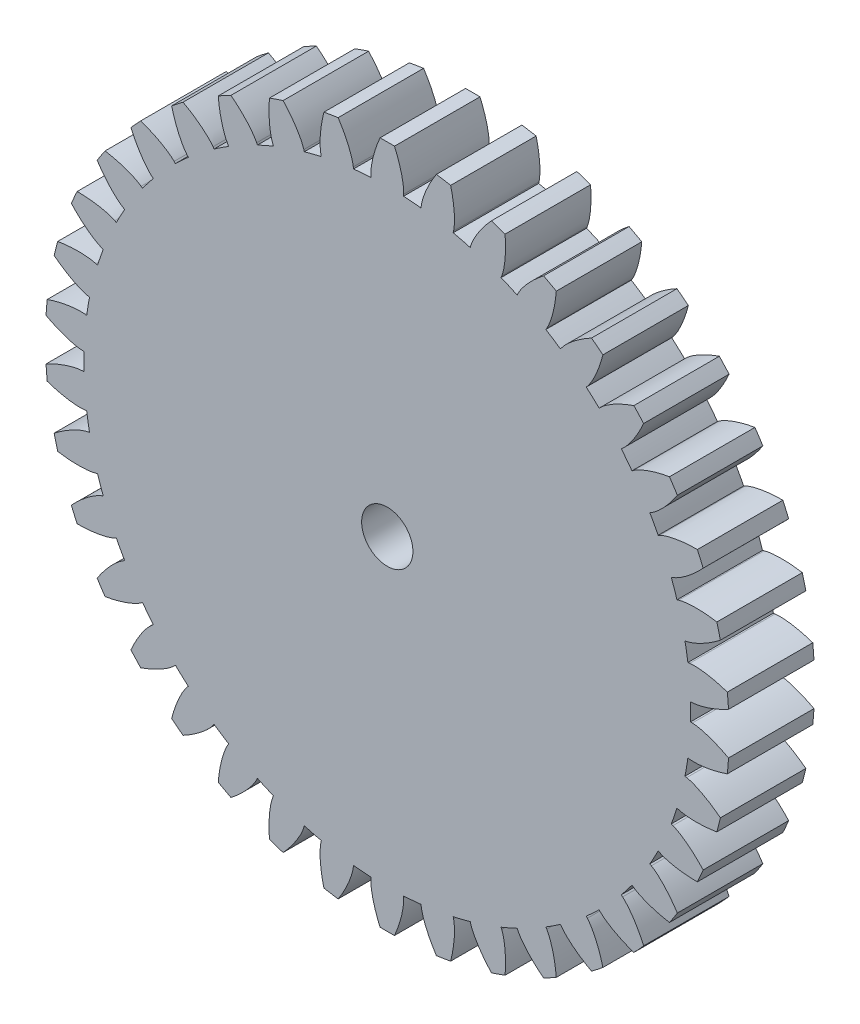
SolidWorks part; units mm, degrees
ref_plane "前视基准面" through (0, 0, 0) normal (0, 0, 1) x (1, 0, 0)
ref_plane "上视基准面" through (0, 0, 0) normal (0, 1, 0) x (1, 0, 0)
ref_plane "右视基准面" through (0, 0, 0) normal (1, 0, 0) x (0, 0, -1)
other "Configuration Table"
sketch "草图1" plane through (0, 0, 0) normal (0, 0, 1) x (1, 0, 0)
  line L0 (0, 0) -> (19, 0) construction
  line L1 (0, 0) -> (18.9838, 0.7852) construction
  line L2 (0, 0) -> (17.8467, 0.5157)
  line L3 (18.9838, 0.7852) -> (18.9838, -0.7852) construction
  line L4 (0, 0) -> (17.8467, -0.5157)
  circle A0 centre (0, 0) radius 20
  circle A1 centre (0, 0) radius 19 construction
  circle A2 centre (0, 0) radius 17.75
  circle A3 centre (0, 0) radius 17.8542 construction
  circle A4 centre (0, 0) radius 1.5
  spline S0 degree 4 poles (17.8467, 0.5157) (17.8807, 0.5167) (17.9484, 0.5207) (18.0833, 0.537) (18.3375, 0.584) (18.6733, 0.6727) (19.1324, 0.8321) (19.6729, 1.0705) (20.4872, 1.506) (21.549, 2.2345) (22.8952, 3.4297) (24.3758, 5.2063) (25.7051, 7.3713) (26.8016, 9.8792) (27.5793, 12.502) (28.0558, 15.1949) (28.2576, 18.0569) (28.1368, 21.6081) (27.4506, 25.7959) (25.9511, 30.4951) (23.4989, 35.3947) (20.7605, 39.3269) (18.0528, 42.4068) (15.5858, 44.7666) (13.4967, 46.526) (11.3039, 48.1534) (9.0163, 49.6461) (6.0541, 51.3408) (2.3486, 53.0976) (-2.1434, 54.7391) (-6.4614, 55.8085) (-9.8217, 56.3712) (-12.2052, 56.6454) (-13.5383, 56.7677) (-14.8361, 56.8491) (-15.854, 56.8967) (-16.9306, 56.9208) (-17.4967, 56.9272) (-18.1867, 56.9272) (-18.7351, 56.9214) (-19.419, 56.9074) (-20.2481, 56.8799) (-21.2082, 56.8323) (-22.3086, 56.7568) (-23.4047, 56.6603) (-24.5006, 56.543) (-25.3196, 56.4395) (-25.8654, 56.3637) (-26.1377, 56.3241) knots 0 0 0 0 0 0.001401 0.002802 0.005604 0.010661 0.015718 0.022839 0.02996 0.048734 0.068727 0.096889 0.125051 0.153212 0.181374 0.209535 0.237696 0.271429 0.327752 0.384075 0.440398 0.496721 0.524883 0.553044 0.581206 0.609367 0.637529 0.66569 0.722013 0.778336 0.834659 0.84874 0.86282 0.876901 0.890982 0.900036 0.909091 0.914773 0.920455 0.926136 0.931818 0.943182 0.954545 0.965909 0.977273 0.988636 1 1 1 1 1 construction
  spline S1 degree 4 poles (17.8467, 0.5157) (17.8807, 0.5167) (17.9484, 0.5207) (18.0833, 0.537) (18.3375, 0.584) (18.6733, 0.6727) (19.1324, 0.8321) (19.6729, 1.0705) (20.4872, 1.506) (21.549, 2.2345) (22.8952, 3.4297) (24.3758, 5.2063) (25.7051, 7.3713) (26.8016, 9.8792) (27.5793, 12.502) (28.0558, 15.1949) (28.2576, 18.0569) (28.1368, 21.6081) (27.4506, 25.7959) (25.9511, 30.4951) (23.4989, 35.3947) (20.7605, 39.3269) (18.0528, 42.4068) (15.5858, 44.7666) (13.4967, 46.526) (11.3039, 48.1534) (9.0163, 49.6461) (6.0541, 51.3408) (2.3486, 53.0976) (-2.1434, 54.7391) (-6.4614, 55.8085) (-9.8217, 56.3712) (-12.2052, 56.6454) (-13.5383, 56.7677) (-14.8361, 56.8491) (-15.854, 56.8967) (-16.7691, 56.9172) (-17.1568, 56.9229) (-17.3562, 56.9247) knots 0 0 0 0 0 0.001401 0.002802 0.005604 0.010661 0.015718 0.022839 0.02996 0.048734 0.068727 0.096889 0.125051 0.153212 0.181374 0.209535 0.237696 0.271429 0.327752 0.384075 0.440398 0.496721 0.524883 0.553044 0.581206 0.609367 0.637529 0.66569 0.722013 0.778336 0.834659 0.84874 0.86282 0.876901 0.890982 0.900036 0.909091 0.909091 0.909091 0.909091 0.909091
  spline S2 degree 4 poles (17.8467, -0.5157) (17.8807, -0.5167) (17.9484, -0.5207) (18.0833, -0.537) (18.3375, -0.584) (18.6733, -0.6727) (19.1324, -0.8321) (19.6729, -1.0705) (20.4872, -1.506) (21.549, -2.2345) (22.8952, -3.4297) (24.3758, -5.2063) (25.7051, -7.3713) (26.8016, -9.8792) (27.5793, -12.502) (28.0558, -15.1949) (28.2576, -18.0569) (28.1368, -21.6081) (27.4506, -25.7959) (25.9511, -30.4951) (23.4989, -35.3947) (20.7605, -39.3269) (18.0528, -42.4068) (15.5858, -44.7666) (13.4967, -46.526) (11.3039, -48.1534) (9.0163, -49.6461) (6.0541, -51.3408) (2.3486, -53.0976) (-2.1434, -54.7391) (-6.4614, -55.8085) (-9.8217, -56.3712) (-12.2052, -56.6454) (-13.5383, -56.7677) (-14.8361, -56.8491) (-15.854, -56.8967) (-16.9306, -56.9208) (-17.4967, -56.9272) (-18.1867, -56.9272) (-18.7351, -56.9214) (-19.419, -56.9074) (-20.2481, -56.8799) (-21.2082, -56.8323) (-22.3086, -56.7568) (-23.4047, -56.6603) (-24.5006, -56.543) (-25.3196, -56.4395) (-25.8654, -56.3637) (-26.1377, -56.3241) knots 0 0 0 0 0 0.001401 0.002802 0.005604 0.010661 0.015718 0.022839 0.02996 0.048734 0.068727 0.096889 0.125051 0.153212 0.181374 0.209535 0.237696 0.271429 0.327752 0.384075 0.440398 0.496721 0.524883 0.553044 0.581206 0.609367 0.637529 0.66569 0.722013 0.778336 0.834659 0.84874 0.86282 0.876901 0.890982 0.900036 0.909091 0.914773 0.920455 0.926136 0.931818 0.943182 0.954545 0.965909 0.977273 0.988636 1 1 1 1 1 construction
  spline S3 degree 4 poles (17.8467, -0.5157) (17.8807, -0.5167) (17.9484, -0.5207) (18.0833, -0.537) (18.3375, -0.584) (18.6733, -0.6727) (19.1324, -0.8321) (19.6729, -1.0705) (20.4872, -1.506) (21.549, -2.2345) (22.8952, -3.4297) (24.3758, -5.2063) (25.7051, -7.3713) (26.8016, -9.8792) (27.5793, -12.502) (28.0558, -15.1949) (28.2576, -18.0569) (28.1368, -21.6081) (27.4506, -25.7959) (25.9511, -30.4951) (23.4989, -35.3947) (20.7605, -39.3269) (18.0528, -42.4068) (15.5858, -44.7666) (13.4967, -46.526) (11.3039, -48.1534) (9.0163, -49.6461) (6.0541, -51.3408) (2.3486, -53.0976) (-2.1434, -54.7391) (-6.4614, -55.8085) (-9.8217, -56.3712) (-12.2052, -56.6454) (-13.5383, -56.7677) (-14.8361, -56.8491) (-15.854, -56.8967) (-16.7691, -56.9172) (-17.1568, -56.9229) (-17.3562, -56.9247) knots 0 0 0 0 0 0.001401 0.002802 0.005604 0.010661 0.015718 0.022839 0.02996 0.048734 0.068727 0.096889 0.125051 0.153212 0.181374 0.209535 0.237696 0.271429 0.327752 0.384075 0.440398 0.496721 0.524883 0.553044 0.581206 0.609367 0.637529 0.66569 0.722013 0.778336 0.834659 0.84874 0.86282 0.876901 0.890982 0.900036 0.909091 0.909091 0.909091 0.909091 0.909091
  point P15 (18.9838, 0)
  dimension "齿顶圆直径" = 40
  dimension "分度圆直径" = 38
  dimension "齿根圆直径" = 35.5
  dimension "基圆直径" = 35.7083
  dimension "内孔直径" = 3
  dimension "渐近线镜像线夹角" = 2.368
extrude "凸台-拉伸1" add sketch "草图1" along normal blind 5 contours A0 | A4
extrude "切除-拉伸1" cut sketch "草图1<3>" along normal through all contours A2 S3 A0 S1 region at (19.0461, 0, 0)
sketch "草图1<3>" plane through (0, 0, 0) normal (0, 0, 1) x (1, 0, 0) same geometry as "草图1"
pattern_circular "阵列(圆周)1" count 38 every 9.474 about axis through (0, 0, 5) along (0, 0, 1) of "切除-拉伸1"
equation "\"m\"= 1'模数"
equation "\"z\"= 38'齿数"
equation "\"a\"= 20度'压力角"
equation "\"d\"= \"m\" * \"z\"'分度圆直径"
equation "\"da\"= ( \"z\" + 2 ) * \"m\"'齿顶圆直径"
equation "\"df\"= ( \"z\" - 2.5 ) * \"m\"'齿根圆直径"
equation "\"s\"= 0.5 * PI * \"m\"'分度圆齿厚"
equation "\"r\"= 0.38 * \"m\"'齿根圆角"
equation "\"B\"= 0.3 * \"d\"'齿厚"
equation "\"db\"= \"m\" * \"z\" * cos ( \"a\" )'基圆直径"
equation "\"rb\"= \"db\" / 2'基圆半径"
equation "\"齿顶圆直径@草图1\"= \"da\""
equation "\"分度圆直径@草图1\"= \"d\""
equation "\"齿根圆直径@草图1\"= \"df\""
equation "\"基圆直径@草图1\"= \"db\""
equation "\"渐近线镜像线夹角@草图1\"= 360 / 4 / \"z\""
equation "\"h\"= 5'齿轮厚度"
equation "\"ir\"= 3'内孔直径"
equation "\"内孔直径@草图1\"= \"ir\""
equation "\"齿轮厚@凸台-拉伸1\"= \"h\""
equation "\"齿轮夹角@阵列(圆周)1\"= 360 / \"z\""
equation "\"齿数@阵列(圆周)1\"= \"z\""
